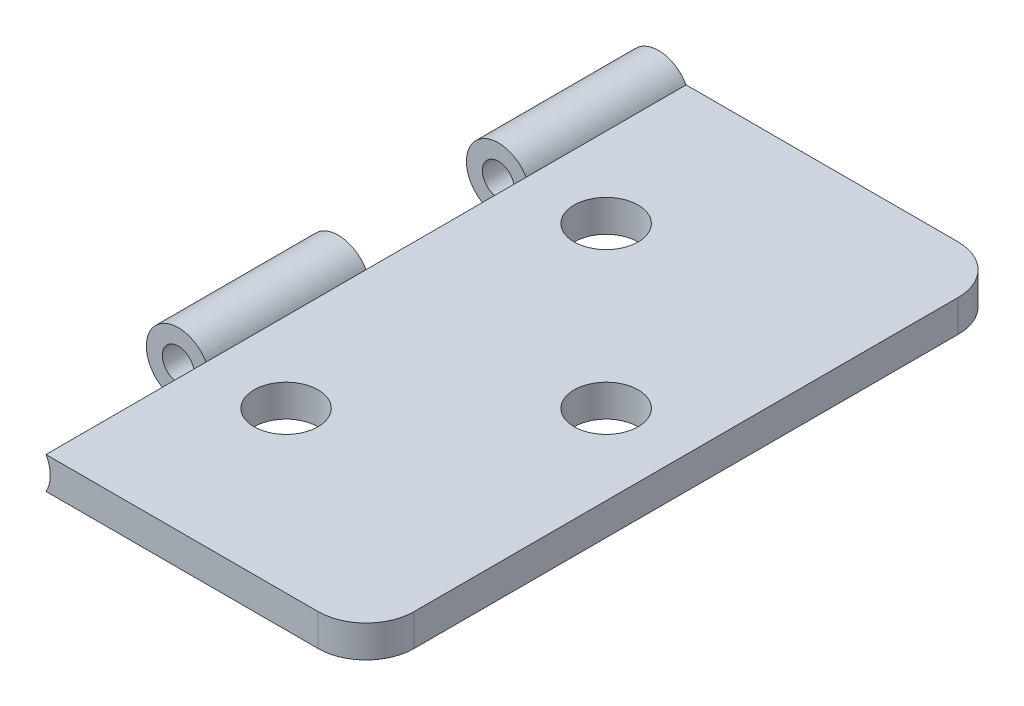
SolidWorks part; units mm, degrees
ref_plane "Front Plane" through (0, 0, 0) normal (0, 0, 1) x (1, 0, 0)
ref_plane "Top Plane" through (0, 0, 0) normal (0, 1, 0) x (1, 0, 0)
ref_plane "Right Plane" through (0, 0, 0) normal (1, 0, 0) x (0, 0, -1)
sketch "Sketch1" plane through (0, 0, 0) normal (0, 0, 1) x (1, 0, 0)
  line L1 (33.4411, 0) -> (33.4411, -2)
  line L2 (33.4411, -2) -> (13.4411, -2)
  line L3 (13.4411, 0) -> (33.4411, 0)
  circle A0 centre (11.709, -1) radius 2
  circle A1 centre (11.709, -1) radius 1
  dimension "D1" = 2
  dimension "D4" = 2
  dimension "D5" = 4
  dimension "D2" = 20
extrude "Boss-Extrude1" add sketch "Sketch1" against normal blind 40 contours A0 L2 L1 L3 region at (23.5315, -1, 0)
extrude "Boss-Extrude2" add sketch "Sketch1<3>" against normal blind 10 from offset 10 contours A0 A1 region at (13.5862, -0.497, 0) offset against normal yes
sketch "Sketch1<3>" plane through (0, 0, 0) normal (0, 0, 1) x (1, 0, 0) same geometry as "Sketch1"
extrude "Boss-Extrude3" add sketch "Sketch1<4>" against normal blind 10 from offset 30 contours A0 A1 region at (13.5862, -0.497, 0) offset against normal yes
sketch "Sketch1<4>" plane through (0, 0, 0) normal (0, 0, 1) x (1, 0, 0) same geometry as "Sketch1"
sketch "Sketch2" plane through (0, 0, 0) normal (0, 1, 0) x (1, 0, 0)
  line L0 (33.4411, 40) -> (33.4411, 0) construction
  circle A0 centre (18.4411, 30) radius 2
  circle A1 centre (18.4411, 10) radius 2
  circle A2 centre (28.4411, 20) radius 2
  dimension "D1" = 4
  dimension "D3" = 10
  dimension "D4" = 5
  dimension "D2" = 5
extrude "Cut-Extrude1" cut sketch "Sketch2" against normal blind 10
fillet "Fillet1" radius 3 1 edges at (33.4411, -1, 0)
fillet "Fillet2" radius 3 1 edges at (33.4411, -1, -40)
